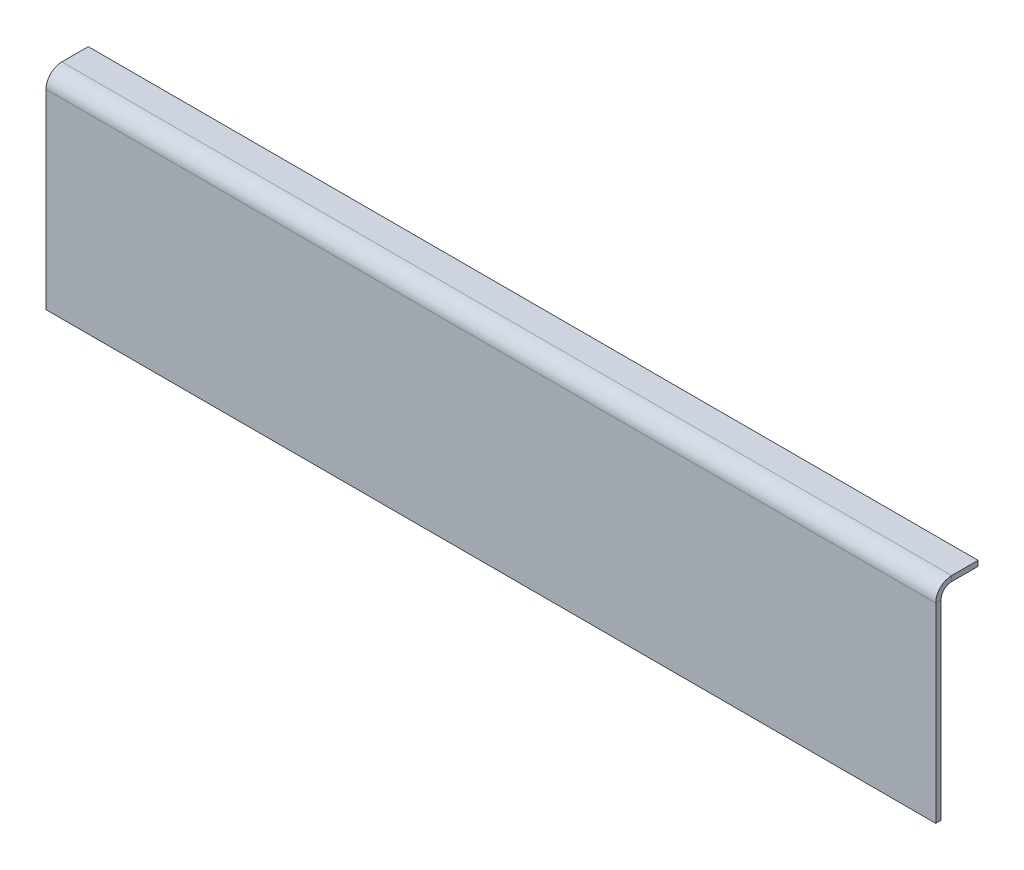
SolidWorks part; units mm, degrees
note: The reader was unsure of these and kept them because the rebuilt part matched: flange length of "Edge-Flange1".
material "6061-T6 (SS)"
ref_plane "X-Y Datum" through (0, 0, 0) normal (0, 0, 1) x (1, 0, 0)
ref_plane "X-Z Datum" through (0, 0, 0) normal (0, 1, 0) x (1, 0, 0)
ref_plane "Y-Z Datum" through (0, 0, 0) normal (1, 0, 0) x (0, 0, -1)
sketch "Sketch1" plane through (0, 0, 0) normal (0, 0, 1) x (1, 0, 0)
  line L1 (0, 0) -> (534.9977, 0)
  line L2 (0, 0) -> (0, 121.1072)
  line L3 (0, 121.1072) -> (534.9977, 121.1072)
  line L4 (534.9977, 0) -> (534.9977, 121.1072)
  dimension "D1" = 534.9977
base flange "Base-Flange1" sketch "Sketch1" thickness 3.175 reverse thickness direction no parameters "D1"=9.525
edge flange "Edge-Flange1" sketch "Sketch8" flange angle 90 flange length 25.4 flange position material outside bend radius 6.35 thickness 3.175 relief rectangular parameters "D6"=10
sketch "Sketch8" plane through (0, 121.1072, -3.175) normal (0, 1, 0) x (1, 0, 0)
  line L2 (0, 0) -> (0, 22.225)
  line L3 (0, 22.225) -> (534.9977, 22.225)
  line L4 (534.9977, 22.225) -> (534.9977, 0)
  line L7 (534.9977, 0) -> (0, 0) construction
  line L8 (534.9977, 0) -> (0, 0)
bend "EdgeBend1" bend radius 6.35 bend angle 90 parameters "D5"=1
sketch "Bend-Lines1" [suppressed] plane through (0, 0, 0) normal (0, 1, 0) x (1, 0, 0)
sketch "Bounding-Box1" [suppressed] plane through (0, 0, 0) normal (0, 1, 0) x (1, 0, 0)
sheet metal parameters "Sheet-Metal1" thickness 3.175 parameters "D1"=9.525
flat pattern "Flat-Pattern1" [suppressed]
sketch "Bend-Lines2" plane through (0, 0, 0) normal (0, 1, 0) x (1, 0, 0)
sketch3d "Bounding-Box2" [suppressed]
  line L0 (0, 0, 0) -> (-534.9977, 0, 0) construction
  line L1 (0, 121.1072, 0) -> (-534.9977, 121.1072, 0) construction
  line L2 (0, 0, 0) -> (0, 121.1072, 0) construction
  line L3 (-534.9977, 0, 0) -> (-534.9977, 121.1072, 0) construction
sheet metal parameters "Sheet-Metal2" thickness 3.175 parameters "D1"=9.525
flat pattern "Flat-Pattern1"
sketch "Bend-Lines2" plane through (0, 0, 0) normal (0, 0, 1) x (1, 0, 0)
  line L0 (534.9977, 120.9913) -> (0, 120.9913) construction
  line L1 (534.9977, 120.9913) -> (0, 120.9913) construction
sketch3d "Bounding-Box2" [suppressed]
  line L0 (0, 0, 0) -> (534.9977, 0, 0) construction
  line L1 (0, 143.1004, 0) -> (534.9977, 143.1004, 0) construction
  line L2 (0, 0, 0) -> (0, 143.1004, 0) construction
  line L3 (534.9977, 0, 0) -> (534.9977, 143.1004, 0) construction
bend of the flat pattern "Flatten-<EdgeBend1>1"
